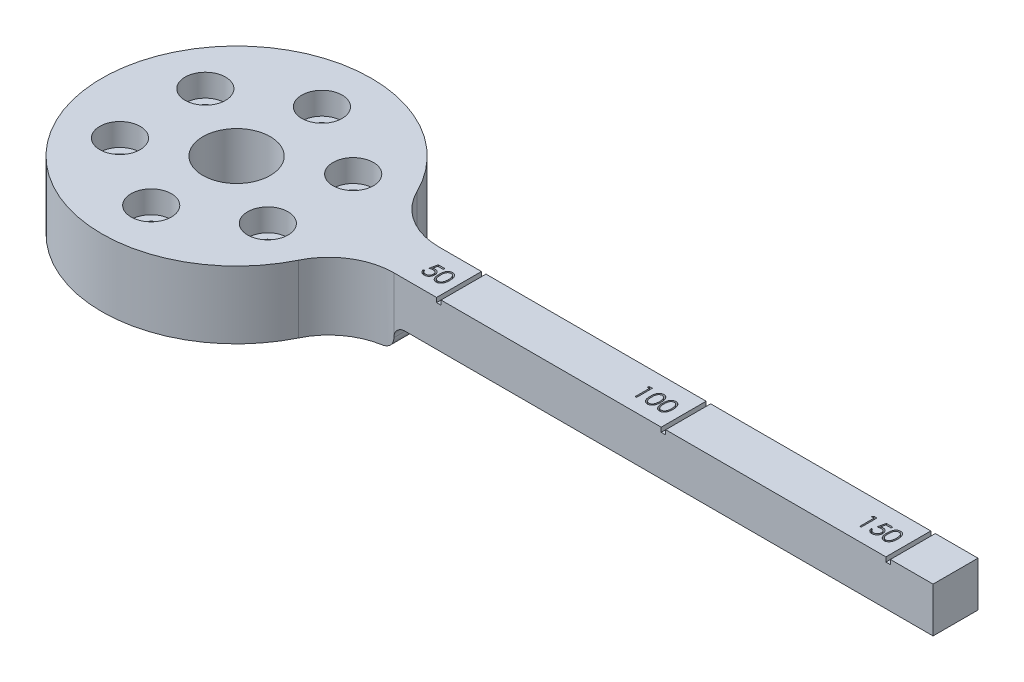
SolidWorks part; units mm, degrees
ref_plane "Front Plane" through (0, 0, 0) normal (0, 0, 1) x (1, 0, 0)
ref_plane "Top Plane" through (0, 0, 0) normal (0, 1, 0) x (1, 0, 0)
ref_plane "Right Plane" through (0, 0, 0) normal (1, 0, 0) x (0, 0, -1)
sketch "Sketch1" plane through (0, 0, 0) normal (0, 1, 0) x (1, 0, 0)
  line L2 (160, 5) -> (160, -5)
  line L3 (160, 5) -> (40, 5)
  line L4 (160, -5) -> (40, -5)
  arc A0 (26.9663, 13.1461) -> (26.9663, -13.1461) centre (0, 0) ccw
  circle A1 centre (0, 0) radius 7.5
  arc A2 (40, -5) -> (26.9663, -13.1461) centre (40, -19.5) ccw
  arc A3 (40, 5) -> (26.9663, 13.1461) centre (40, 19.5) cw
  point P1 (0, 0)
  point P7 (160, 0)
  point P10 (44.2809, -5)
  point P11 (37.8934, 5)
  point P12 (29.5804, 5)
  point P13 (29.5804, -5)
  dimension "D2" = 40
  dimension "D3" = 30
  dimension "D4" = 15
  dimension "D1" = 10
  dimension "D5" = 160
extrude "Boss-Extrude1" add sketch "Sketch1" along normal blind 15
sketch "Sketch2" plane through (0, 15, 0) normal (0, 1, 0) x (1, 0, 0)
  circle A0 centre (0, 0) radius 19 construction
  circle A1 centre (0, 19) radius 4.5
  circle A2 centre (16.4545, 9.5) radius 4.5
  circle A3 centre (16.4545, -9.5) radius 4.5
  circle A4 centre (0, -19) radius 4.5
  circle A5 centre (-16.4545, -9.5) radius 4.5
  circle A6 centre (-16.4545, 9.5) radius 4.5
  point P21 (0, 0)
  dimension "D1" = 38
  dimension "D2" = 9
  dimension "D3" = 6
extrude "Cut-Extrude1" cut sketch "Sketch2" against normal blind 5
sketch "Sketch3" plane through (0, 10, 0) normal (0, 1, 0) x (1, 0, 0)
  circle A0 centre (0, 19) radius 2.75
  circle A1 centre (16.4545, 9.5) radius 2.75
  circle A2 centre (16.4545, -9.5) radius 2.75
  circle A3 centre (0, -19) radius 2.75
  circle A4 centre (-16.4545, -9.5) radius 2.75
  circle A5 centre (-16.4545, 9.5) radius 2.75
  point P19 (0, 0)
  dimension "D1" = 5.5
  dimension "D2" = 6
extrude "Cut-Extrude2" cut sketch "Sketch3" against normal through all
sketch "Sketch4" plane through (0, 15, 0) normal (0, 1, 0) x (1, 0, 0)
  line L0 (49.5, 5) -> (49.5, -5)
  line L1 (160, 5) -> (40, 5) construction
  line L2 (40, -5) -> (160, -5) construction
  line L3 (50.5, 5) -> (50.5, -5)
  line L4 (99.5, 5) -> (99.5, -5)
  line L5 (100.5, 5) -> (100.5, -5)
  line L6 (149.5, 5) -> (149.5, -5)
  line L7 (150.5, 5) -> (150.5, -5)
  line L8 (49.5, 5) -> (50.5, 5)
  line L9 (49.5, -5) -> (50.5, -5)
  line L10 (99.5, 5) -> (100.5, 5)
  line L11 (99.5, -5) -> (100.5, -5)
  line L12 (149.5, 5) -> (150.5, 5)
  line L13 (149.5, -5) -> (150.5, -5)
  dimension "D1" = 1
  dimension "D2" = 49.5
  dimension "D3" = 1
  dimension "D4" = 99.5
  dimension "D5" = 1
  dimension "D6" = 149.5
extrude "Cut-Extrude3" cut sketch "Sketch4" against normal blind 1
sketch "Sketch5" plane through (0, 15, 0) normal (0, 1, 0) x (1, 0, 0)
  line L0 (49.5, 5) -> (49.5, -5) construction
  line L1 (99.5, 5) -> (99.5, -5) construction
  line L2 (149.5, 5) -> (149.5, -5) construction
  line L3 (49.5, 5) -> (40, 5) construction
  text T0 "50"
  text T1 "100"
  text T2 "150"
  point P3 (140.4674, -0.8162)
  point P4 (0, 0)
  point P5 (0, 0)
  point P6 (141.7124, -1.8238)
  point P7 (138.0336, -1.9552)
  dimension "D1" = 7
  dimension "D2" = 10
  dimension "D3" = 10
  dimension "D4" = 7
extrude "Cut-Extrude4" cut sketch "Sketch5" against normal blind 1
sketch "Sketch6" plane through (0, 0, 0) normal (0, 0, 1) x (1, 0, 0)
  line L0 (40, 15) -> (40, 0) construction
  line L1 (160, 0) -> (40, 0)
  line L2 (160, 0) -> (160, 5)
  line L3 (160, 5) -> (40, 5)
  line L4 (40, 0) -> (40, 5)
  dimension "D1" = 5
extrude "Cut-Extrude5" cut sketch "Sketch6" along normal mid plane 10
fillet "Fillet1" radius 2.5 2 edges at (40, 5, 0) (40, 0, 0)
